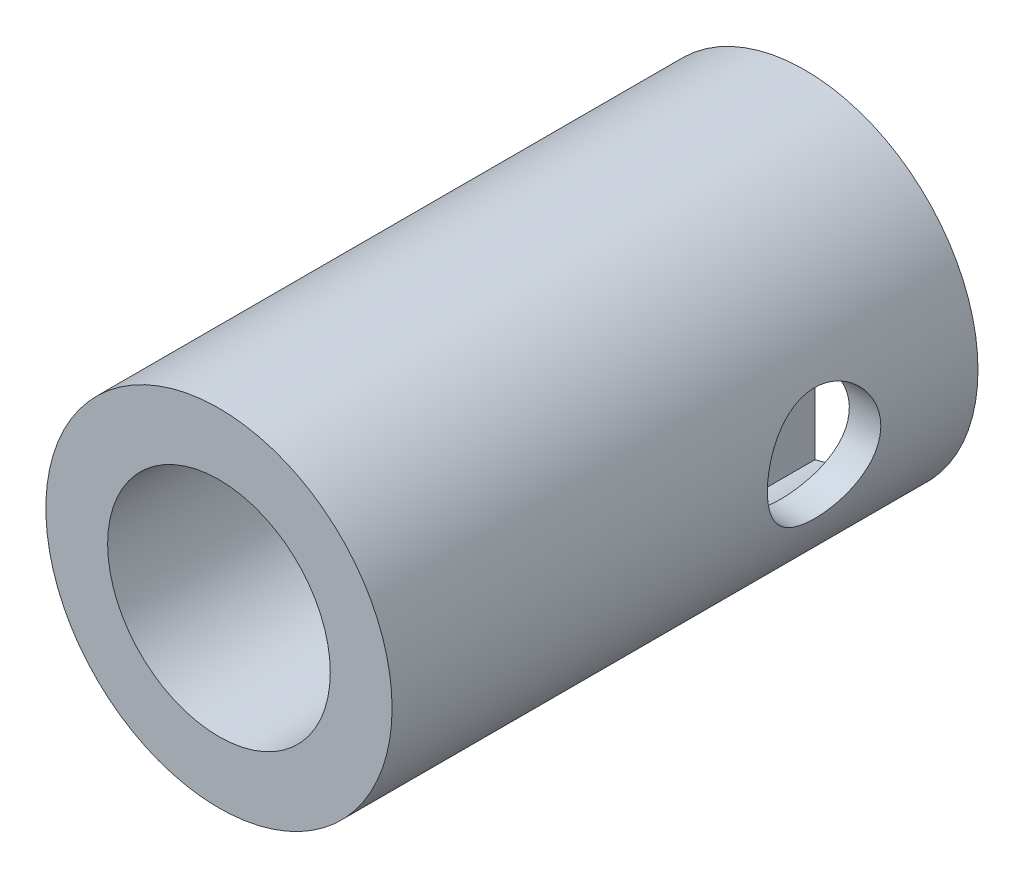
SolidWorks part; units mm, degrees
material "PET"
ref_plane "Front Plane" through (0, 0, 0) normal (0, 0, 1) x (1, 0, 0)
ref_plane "Top Plane" through (0, 0, 0) normal (0, 1, 0) x (1, 0, 0)
ref_plane "Right Plane" through (0, 0, 0) normal (1, 0, 0) x (0, 0, -1)
sketch "Sketch1" plane through (0, 0, 0) normal (0, 0, 1) x (1, 0, 0)
  circle A0 centre (0, 0) radius 4.1275
  dimension "D1" = 8.255
extrude "Boss-Extrude1" add sketch "Sketch1" along normal blind 6.35 and the other way blind 7.62
sketch "Sketch2" plane through (0, 0, -7.62) normal (0, 0, -1) x (-1, 0, 0)
  line L0 (-0.746, -3.2939) -> (-0.746, 3.2939)
  line L1 (-1, 3.0923) -> (-1, -3.0923) construction
  line L2 (0, 0) -> (0, -4.1275) construction
  line L3 (0.746, -3.2939) -> (0.746, 3.2939)
  arc A2 (-0.746, 3.2939) -> (-0.746, -3.2939) centre (0, 0) ccw
  circle A3 centre (0, 0) radius 4.1275 construction
  arc A4 (0.746, -3.2939) -> (0.746, 3.2939) centre (0, 0) ccw
  dimension "D1" = 0.254
extrude "Cut-Extrude1" cut sketch "Sketch2" against normal blind 7.874
ref_plane "Plane1" through (-4.1275, 0, 0) normal (-1, 0, 0) x (0, 0, 1)
hole_wizard "#2 Clearance Hole1" positions "Sketch4" profile "Sketch3" hole size "#2" standard "ANSI Inch" end condition through all
sketch "Sketch4" plane through (-4.1275, 0, 0) normal (-1, 0, 0) x (0, 0, 1)
  point P0 (-3.95, 0)
sketch "Sketch3" plane through (-4.1275, 0, -3.95) normal (0, 1, 0) x (0, 0, 1)
  line L0 (0, 0) -> (0, 8.255)
  line L1 (0, 8.255) -> (1.3525, 8.255)
  line L2 (1.3525, 8.255) -> (1.3525, 0)
  line L5 (1.3525, 0) -> (0, 0)
  line L11 (0, -6.35) -> (0, 107.95) construction
  dimension "Thru Hole Dia." = 2.7051
  dimension "Thru Hole Depth" = 8.255
hole_wizard "Hole1" positions "Sketch6" profile "Sketch5" legacy
sketch "Sketch6" plane through (0, 0, 6.35) normal (0, 0, 1) x (1, 0, 0)
  point P0 (0, 0)
sketch "Sketch5" plane through (0, 0, 6.35) normal (1, 0, 0) x (0, -1, 0)
  line L0 (0, 0) -> (0, 3.81)
  line L1 (0, 3.81) -> (2.5273, 3.81)
  line L2 (2.5273, 3.81) -> (2.6543, 0)
  line L3 (2.6543, 0) -> (0, 0)
  line L4 (0, 110) -> (0, -10) construction
  dimension "Minor Diameter" = 5.0546
  dimension "Depth" = 3.81
  dimension "Major Diameter" = 5.3086
chamfer "Chamfer1" distance 0.508 angle 45 4 edges at (3.3773, 0, -7.62) (0.746, 0, -7.62) (-3.3773, 0, -7.62) (-0.746, 0, -7.62)
